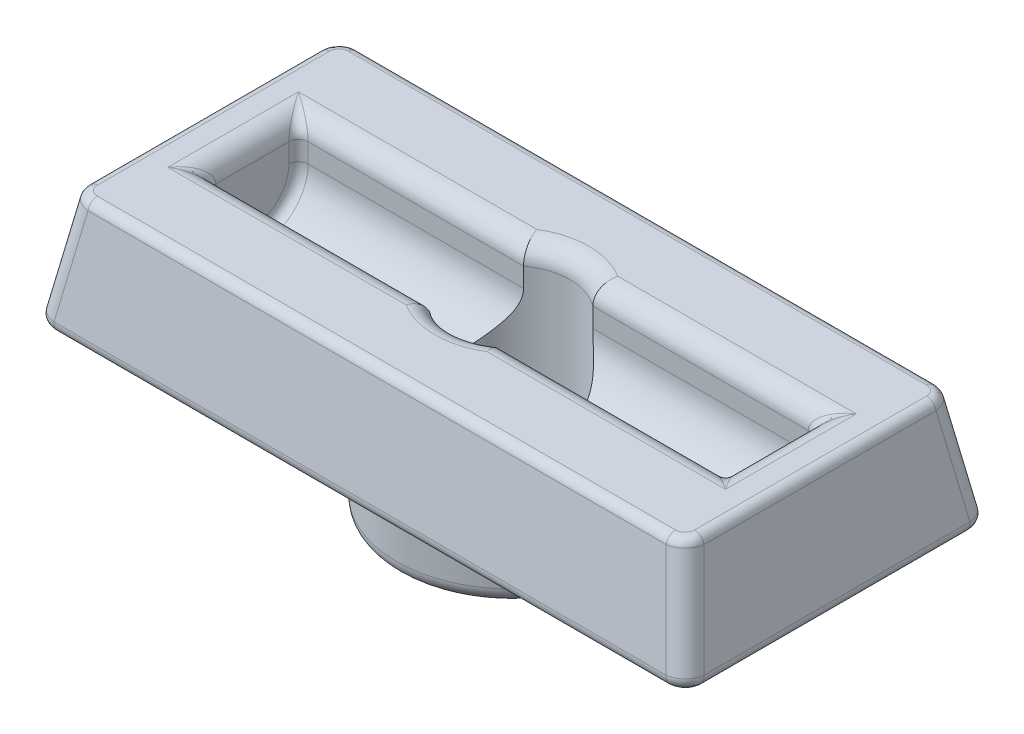
SolidWorks part; units mm, degrees
ref_plane "Front plane" through (0, 0, 0) normal (0, 0, 1) x (1, 0, 0)
ref_plane "Top plane" through (0, 0, 0) normal (0, 1, 0) x (1, 0, 0)
ref_plane "Right plane" through (0, 0, 0) normal (1, 0, 0) x (0, 0, -1)
ref_axis "Axis X" through (0, 0, 0) along (1, 0, 0)
ref_axis "Axis Y" through (0, 0, 0) along (0, 1, 0)
ref_axis "Axis Z" through (0, 0, 0) along (0, 0, 1)
sketch "Sketch1" plane through (0, 0, 0) normal (0, 1, 0) x (1, 0, 0)
  line L1 (-8.5, 4) -> (8.5, 4)
  line L2 (-8.5, 4) -> (-8.5, -4)
  line L3 (-8.5, -4) -> (8.5, -4)
  line L4 (8.5, 4) -> (8.5, -4)
  line L5 (-8.5, 4) -> (8.5, -4) construction
  line L6 (-8.5, -4) -> (8.5, 4) construction
  point P0 (0, 0)
  dimension "D1" = 8
  dimension "D2" = 17
extrude "Extrude1" add sketch "Sketch1" along normal blind 3 draft 10
sketch "Sketch2" plane through (0, 0, 0) normal (1, 0, 0) x (0, 0, -1)
  line L0 (-4, 0) -> (4, 0) construction
  line L1 (-3.471, 3) -> (3.471, 3) construction
  line L2 (-1.2, 2) -> (1.2, 2) construction
  line L3 (-1.2, 2) -> (-1.2, 3)
  line L4 (-1.2, 3) -> (1.2, 3)
  line L5 (1.2, 2) -> (1.2, 3)
  line L6 (0, 2) -> (0, 0) construction
  arc A0 (-1.2, 2) -> (1.2, 2) centre (0, 2) ccw
  arc A1 (0.6633, 3) -> (-1.2, 2) centre (0, 2) ccw construction
  arc A2 (1.2, 2) -> (0.6633, 3) centre (0, 2) ccw construction
  dimension "D2" = 2.4
  dimension "D1" = 2
extrude "Extrude2" cut sketch "Sketch2" against normal blind 6.75 and the other way blind 6.75
sketch "Sketch4" plane through (0, 0, 0) normal (0, -1, 0) x (1, 0, 0)
  circle A0 centre (0, 0) radius 3
  dimension "D1" = 6
extrude "Extrude4" add sketch "Sketch4" along normal blind 2
sketch "Sketch3" plane through (0, 3, 0) normal (0, 1, 0) x (1, 0, 0)
  circle A0 centre (0, 0) radius 1.5
  dimension "D1" = 3
extrude "Extrude3" cut sketch "Sketch3" against normal through all
fillet "Fillet1" radius 0.5 12 edges at (-3.825, 3, -1.2) (-6.75, 3, 0) (-3.825, 3, 1.2) (0, 3, 1.5) (3.825, 3, 1.2) (6.75, 3, 0) (3.825, 3, -1.2) (0, 3, -1.5) (-8.2355, 1.5, -3.7355) (-8.2355, 1.5, 3.7355) (8.2355, 1.5, 3.7355) (8.2355, 1.5, -3.7355)
fillet "Fillet3" radius 0.25 26 edges at (-7.8277, 3, -3.3277) (0, 3, -3.471) (7.8277, 3, -3.3277) (7.971, 3, 0) (7.8277, 3, 3.3277) (0, 3, 3.471) (-7.8277, 3, 3.3277) (6.8964, 2.8536, 1.3464) (6.75, 2.25, 1.2) (6.8964, 2.8536, -1.3464) (6.75, 2.25, -1.2) (-6.8964, 2.8536, 1.3464) (-6.75, 2.25, 1.2) (-6.8964, 2.8536, -1.3464) (-6.75, 2.25, -1.2) (-7.971, 3, 0) (6.75, 0.8, 0) (-6.75, 0.8, 0) (0, 0, 4) (8.3567, 0, 3.8567) (8.5, 0, 0) (8.3567, 0, -3.8567) (-8.3567, 0, 3.8567) (-8.5, 0, 0) (-8.3567, 0, -3.8567) (0, 0, -4)
fillet "Fillet4" radius 0.4 1 edges at (0, -2, -3)
equation "\"motor_D\"= 49'Motor diameter"
equation "\"motor_H\"= 19'Motor heigh"
equation "\"motor_d1\"= 38.5'Seating diameter of screws on the fixed part of the motor"
equation "\"motor_s1\"= 2.5'Screws diameter on the fixed part of motor"
equation "\"motor_d2\"= 25'Seating diameter of screws on the moving part of the motor (if this parameter is not determine, write 0)"
equation "\"motor_s2\"= 3'Screws diameter on the moving part of motor"
equation "\"motor_Dc\"= 5'Central hole diameter of motor"
equation "\"bearing_d1\"= 6'Bearing inner diameter"
equation "\"bearing_d2\"= 17'Bearing external diameter"
equation "\"bearing h\"= 6'Bearing heigh"
equation "\"pin_d\"= 2'Pin diameter"
equation "\"pin_h\"= 13'Pin heigh"
equation "\"magnet_d1\"= 5'Magnet inner diameter"
equation "\"magnet_d2\"= 9.5'Magnet external diameter"
equation "\"magnet_h\"= 3'Magnet heigh"
equation "\"D1@Sketch1\"=\"pin_d\"+6"
equation "\"D2@Sketch1\"=\"pin_h\"+4"
equation "\"D1@Extrude1\"=\"pin_d\"+1"
equation "\"D1@Sketch2\"=\"pin_d\"/2+1"
equation "\"D2@Sketch2\"=\"pin_d\"+\"print_offset\"*2"
equation "\"D1@Extrude2\"=(\"pin_h\"+0.5)/2"
equation "\"D2@Extrude2\"=(\"pin_h\"+0.5)/2"
equation "\"D1@Sketch3\"= \"bearing_d1\" / 2"
equation "\"D1@Sketch4\"=\"bearing_d1\""
equation "\"D1@Extrude4\"=\"bearing h\"/3"
equation "\"motor_a2\"= 0'Seating parameter in rectangle of screws on the moving part of the motor"
equation "\"motor_b2\"= 0'Seating parameter in rectangle of screws on the moving part of the motor"
equation "\"motor_cmd\"= 17'Central magnet mount diameter"
equation "\"motor_cmh\"= 1'Central magnet mount heigh (if not write 0)"
equation "\"motor_whR\"= 17'Distance from center of motor to wires"
equation "\"print_offset\"= 0.2'Offset for printing holes"
equation "\"ft_sensor_d1\"= 9.8"
equation "\"ft_sensor_d2\"= 24.9"
equation "\"ft_sensor_d3\"= 22.6'Inner diameter of "
equation "\"ft_sensor_h\"= 7.1"
equation "\"ft_sensor_whD\" = 5"
